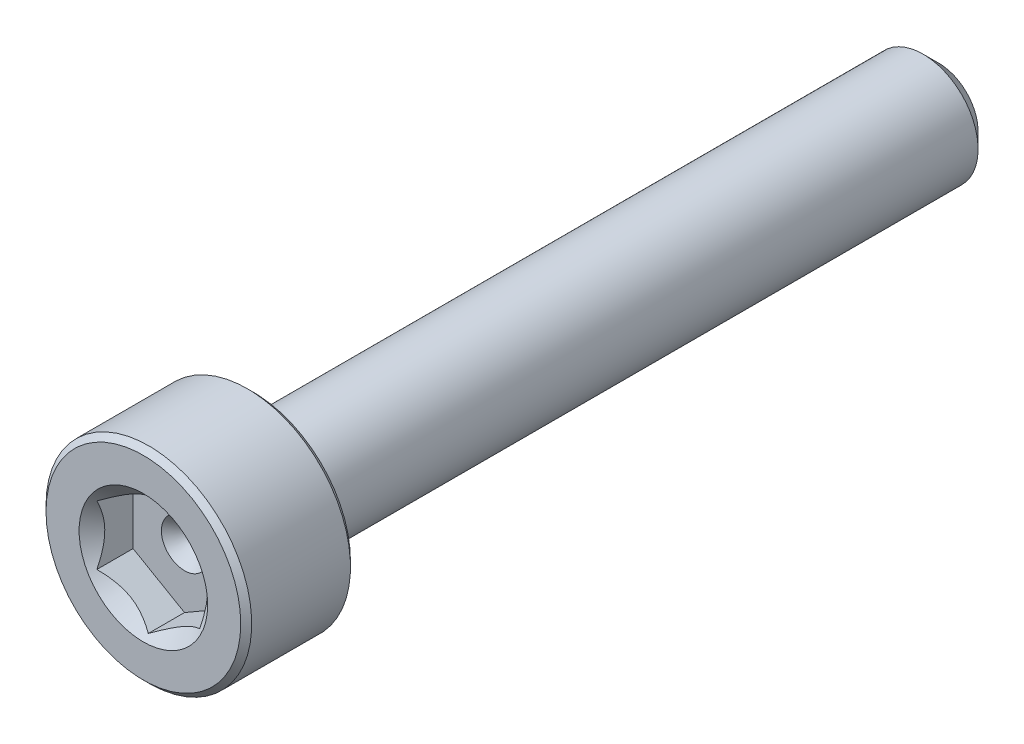
SolidWorks part; units mm, degrees
ref_plane "Front Plane" through (0, 0, 0) normal (0, 0, 1) x (1, 0, 0)
ref_plane "Top Plane" through (0, 0, 0) normal (0, 1, 0) x (1, 0, 0)
ref_plane "Right Plane" through (0, 0, 0) normal (1, 0, 0) x (0, 0, -1)
sketch "Sketch1" plane through (0, 0, 0) normal (1, 0, 0) x (0, 0, -1)
  line L0 (-5.8, 0) -> (5.8, 0) construction
  line L1 (5.8, 0) -> (5.8, 0.5727) construction
  line L2 (5.8, 0.5727) -> (5.5727, 0.8) construction
  line L3 (5.5727, 0.8) -> (5.5375, 0.8) construction
  line L4 (5.5375, 0.8) -> (-4.2, 0.8) construction
  line L5 (-4.2, 0.8) -> (-4.2, 1.5) construction
  line L6 (-4.2, 1.5) -> (-5.8, 1.5) construction
  line L7 (-5.8, 1.5) -> (-5.8, 0) construction
  line L8 (5.8, 0.5727) -> (5.8, 0.8) construction
  line L9 (5.7781, 0.8379) -> (5.9531, 0.5348) construction
  line L10 (5.9531, 0.5348) -> (6.1281, 0.8379) construction
  line L11 (6.1281, 0.8379) -> (5.7781, 0.8379) construction
  line L12 (5.9531, 0.8379) -> (5.9531, 0.8) construction
  line L13 (5.9531, 0.5348) -> (5.9531, 0.5727) construction
  line L14 (5.9313, 0.5727) -> (5.975, 0.5727) construction
  line L15 (5.8, 0.8) -> (6.1063, 0.8) construction
  line L16 (5.7891, 0.8189) -> (6.1172, 0.8189) construction
  line L17 (5.8, 0) -> (5.8, -0.8) construction
  line L18 (-4.28, 1.5) -> (-4.2, 1.42) construction
  line L19 (-5.72, 1.5) -> (-5.8, 1.42) construction
  line L20 (-4.2, 0.8) -> (-4.2, 0) construction
  line L21 (-4.2, 0.4) -> (-0.8667, 0.4) construction
  line L22 (-0.8667, 0.4) -> (2.4667, 0.4) construction
  line L23 (2.4667, 0.4) -> (5.8, 0.4) construction
  line L24 (-0.8667, 0.4) -> (-0.8667, 0.8) construction
  line L25 (-0.8667, 0.8) -> (-0.8667, 1.5) construction
  line L26 (2.4667, 0.4) -> (2.4667, 1.5) construction
  point P0 (-5.8, 0.75)
  point P3 (4.925, 0.8)
  point P4 (0, 0)
  point P18 (2.4667, 0.8)
  point P22 (5.9531, 0.5727)
  point P24 (5.5375, 0.8)
  point P25 (5.9531, 0.8)
  point P28 (5.9531, 0.8189)
  point P29 (4.925, -0.8)
  point P30 (-0.8667, 0.8)
  point P31 (-5, 1.5)
  point P37 (-4.48, 1.5)
  point P38 (-5.68, 1.5)
  point P45 (-0.8667, 0.4)
  point P46 (2.4667, 0.4)
  dimension "D2" = 0.0437
  dimension "D7" = 0.08
  dimension "D8" = 0.08
  dimension "D9" = 0.08
  dimension "D10" = 0.04
  dimension "D11" = 0.2
  dimension "Drive Size" = 1.5
  dimension "Head Diameter" = 3
  dimension "Head Height" = 1.6
  dimension "Thread Pitch" = 0.35
  dimension "Thread Size" = 1.6
  dimension "Length" = 10
  dimension "D12" = 0.2625
  dimension "D4" = 0.875
  dimension "D3" = 45
sketch "Sketch2" plane through (0, 0, 0) normal (1, 0, 0) x (0, 0, -1)
  line L0 (-5.8, 0) -> (-5.8, 1.42)
  line L1 (-5.72, 1.5) -> (-4.28, 1.5)
  line L2 (-4.2, 1.42) -> (-4.2, 1)
  line L4 (5.5727, 0.8) -> (5.8, 0.5727)
  line L5 (5.8, 0.5727) -> (5.8, 0)
  line L6 (-4.2, 1.5) -> (-5.8, 1.5) construction
  line L7 (5.8, 0) -> (-5.8, 0)
  line L8 (-5.72, 1.5) -> (-5.8, 1.42) construction
  line L10 (-5.72, 1.5) -> (-5.8, 1.42)
  line L14 (-4.28, 1.5) -> (-4.2, 1.42) construction
  line L16 (-4.28, 1.5) -> (-4.2, 1.42)
  line L17 (-4.2, 0.8) -> (-4.2, 1.5) construction
  line L19 (-4, 0.8) -> (5.5727, 0.8)
  line L20 (5.5375, 0.8) -> (-4.2, 0.8) construction
  arc A1 (-4.2, 1) -> (-4, 0.8) centre (-4, 1) ccw
  dimension "D3" = 0.2
revolve "Revolve1" add sketch "Sketch2" angle 360 about L7
sketch "Sketch3" plane through (0, 0, 5.8) normal (0, 0, 1) x (1, 0, 0)
  line L1 (0.75, -0.433) -> (0.75, 0.433)
  line L2 (0.75, 0.433) -> (0, 0.866)
  line L3 (0, 0.866) -> (-0.75, 0.433)
  line L4 (-0.75, 0.433) -> (-0.75, -0.433)
  line L5 (-0.75, -0.433) -> (0, -0.866)
  line L6 (0, -0.866) -> (0.75, -0.433)
  circle A0 centre (0, 0) radius 0.75 construction
  circle A1 centre (0, 0) radius 1.5 construction
  circle A2 centre (0, 0) radius 1.5 construction
  circle A3 centre (0, 0) radius 0.866 construction
  point P13 (0, 0)
extrude "Cut-Extrude1" cut sketch "Sketch3" against normal offset from surface (0.6 mm away) 1 up to face at (-1.42, 0, 4.2)
sketch "Sketch4" plane through (0, 0, 5.8) normal (0, 0, 1) x (1, 0, 0)
  circle A0 centre (0, 0) radius 0.9375
  dimension "D1" = 1.875
extrude "Cut-Extrude2" cut sketch "Sketch4" against normal up to vertex (0.8 mm away) draft 45 up to point (0, 1.5, 5)
sketch "Sketch11" plane through (0, 0, 0) normal (1, 0, 0) x (0, 0, -1)
  line L0 (-5.8, 0) -> (5.8, 0) construction
  line L1 (-5.8, 0) -> (5.8, 0) construction
  line L2 (-2.325, 0) -> (-2.325, 0.8) construction
  line L3 (5.5375, 0.8) -> (-4.2, 0.8) construction
  line L4 (3.925, 0) -> (3.925, 0.8) construction
  line L6 (5.8, 0.5727) -> (5.8, 0.8) construction
  point P2 (-2.325, 0)
  point P3 (3.925, 0)
  dimension "D1" = 1.875
  dimension "D2" = 1.875
sketch "Sketch6" [suppressed] plane through (0, 0, -5.8) normal (0, 0, -1) x (-1, 0, 0)
  circle A0 centre (0, 0) radius 0.8
curve "Helix/Spiral1" [suppressed] pitch 0.35 height 10.35 turns 29.5714
sketch "Sketch10" [suppressed] plane through (0, 0, 0) normal (1, 0, 0) x (0, 0, -1)
  line L0 (-4, -1.5) -> (-4, 1.5)
  line L5 (-5.8, 0) -> (5.8, 0) construction
  line L6 (-4, 0.8) -> (-4, -0.8) construction
  point P3 (-4, 0)
split "Split1" [suppressed] bodies to split 106
sketch "Sketch7" [suppressed] plane through (0, 0, 0) normal (1, 0, 0) x (0, 0, -1)
  line L0 (5.7891, 0.8189) -> (6.1172, 0.8189)
  line L1 (6.1172, 0.8189) -> (5.975, 0.5727)
  line L2 (5.975, 0.5727) -> (5.9313, 0.5727)
  line L3 (5.9313, 0.5727) -> (5.7891, 0.8189)
sweep "Cut-Sweep1" [suppressed] cut profiles "Sketch7" path "Helix/Spiral1"
sketch "Sketch8" [suppressed] plane through (0, 0, 0) normal (1, 0, 0) x (0, 0, -1)
  line L0 (-4.2, 0) -> (-4.2, 0.8)
  line L1 (-4, -0.8) -> (-4, 0.8) construction
  line L2 (-4.2, 0.8) -> (-4, 0.8)
  line L4 (-4, 0.8) -> (-3.5381, 0)
  line L5 (-3.5381, 0) -> (-4.2, 0)
  line L6 (5.5375, 0.8) -> (-4.2, 0.8) construction
  line L7 (-5.8, 0) -> (5.8, 0) construction
  dimension "D1" = 60
revolve "Revolve2" [suppressed] add sketch "Sketch8" angle 360 about L5
equation "\"D2@Sketch1\" = \"Thread Pitch@Sketch1\" / 8"
equation "\"D4@Helix/Spiral1\" = \"Thread Pitch@Sketch1\""
equation "\"D7@Sketch1\" = \"Head Height@Sketch1\" * .05"
equation "\"D8@Sketch1\"=\"D7@Sketch1\""
equation "\"D9@Sketch1\"=\"D7@Sketch1\""
equation "\"D10@Sketch1\"=\"D7@Sketch1\"/2"
equation "\"D11@Sketch1\"=\"D10@Sketch1\"*5"
equation "\"D4@Sketch1\"=\"Thread Pitch@Sketch1\"*2.5"
equation "\"D12@Sketch1\"=\"Thread Pitch@Sketch1\"*.75"
equation "\"D3@Helix/Spiral1\"=\"Length@Sketch1\"+\"Thread Pitch@Sketch1\""
equation "\"D1@Sketch11\"=\"Length@Sketch1\"*0.1875"
equation "\"D2@Sketch11\"=\"D1@Sketch11\""
equation "\"D1@Sketch4\"=\"Drive Size@Sketch1\"*1.25"
